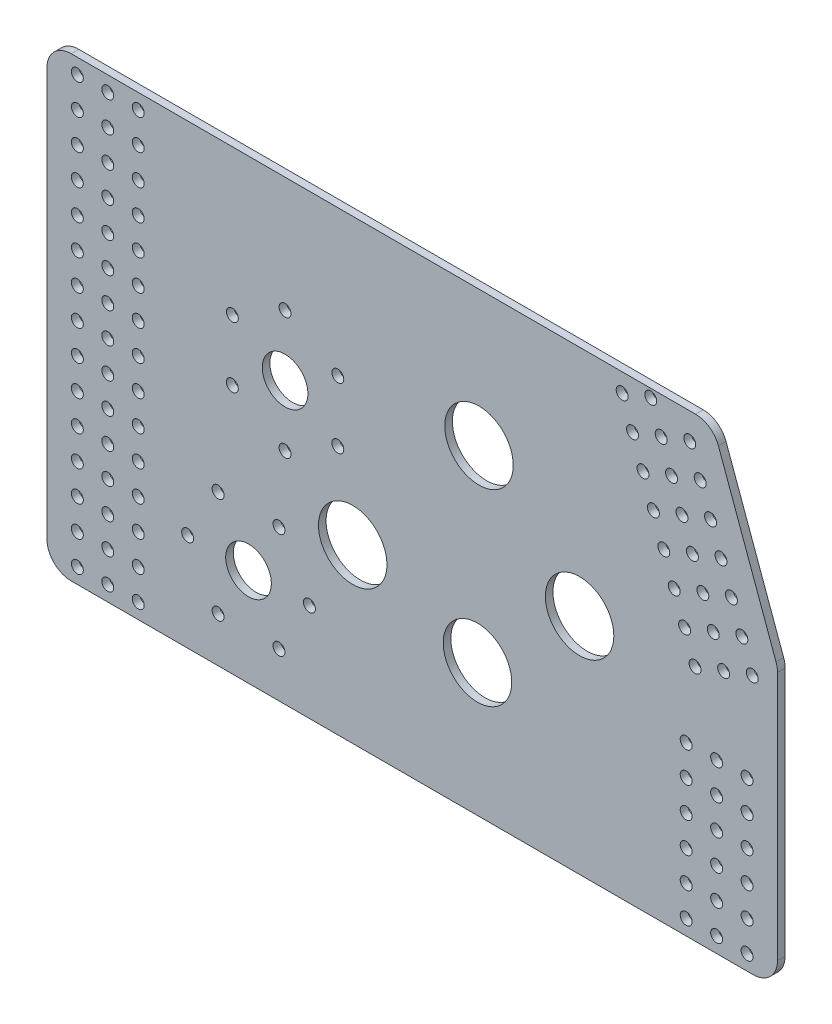
SolidWorks part; units mm, degrees
ref_plane "Front Plane" through (0, 0, 0) normal (0, 0, 1) x (1, 0, 0)
ref_plane "Top Plane" through (0, 0, 0) normal (0, 1, 0) x (1, 0, 0)
ref_plane "Right Plane" through (0, 0, 0) normal (1, 0, 0) x (0, 0, -1)
sketch "Sketch1" plane through (0, 0, 0) normal (0, 0, 1) x (1, 0, 0)
  line B0 (-152.4, 0) -> (152.4, 0)
  line B1 (152.4, 0) -> (152.4, 116.0843)
  line B2 (152.4, 116.0843) -> (125.3149, 190.5)
  line B3 (125.3149, 190.5) -> (-152.4, 190.5)
  line B4 (-152.4, 190.5) -> (-152.4, 0)
  circle B5 centre (-139.7, 184.15) radius 2.4892
  circle B6 centre (-127, 184.15) radius 2.4892
  circle B7 centre (-114.3, 184.15) radius 2.4892
  circle B8 centre (-127, 171.45) radius 2.4892
  circle B9 centre (-114.3, 171.45) radius 2.4892
  circle B10 centre (-127, 158.75) radius 2.4892
  circle B11 centre (-114.3, 158.75) radius 2.4892
  circle B12 centre (-127, 146.05) radius 2.4892
  circle B13 centre (-114.3, 146.05) radius 2.4892
  circle B14 centre (-127, 133.35) radius 2.4892
  circle B15 centre (-114.3, 133.35) radius 2.4892
  circle B16 centre (-127, 120.65) radius 2.4892
  circle B17 centre (-114.3, 120.65) radius 2.4892
  circle B18 centre (-127, 107.95) radius 2.4892
  circle B19 centre (-114.3, 107.95) radius 2.4892
  circle B20 centre (-127, 95.25) radius 2.4892
  circle B21 centre (-114.3, 95.25) radius 2.4892
  circle B22 centre (-127, 82.55) radius 2.4892
  circle B23 centre (-114.3, 82.55) radius 2.4892
  circle B24 centre (-127, 69.85) radius 2.4892
  circle B25 centre (-114.3, 69.85) radius 2.4892
  circle B26 centre (-127, 57.15) radius 2.4892
  circle B27 centre (-114.3, 57.15) radius 2.4892
  circle B28 centre (-127, 44.45) radius 2.4892
  circle B29 centre (-114.3, 44.45) radius 2.4892
  circle B30 centre (-127, 31.75) radius 2.4892
  circle B31 centre (-114.3, 31.75) radius 2.4892
  circle B32 centre (-127, 19.05) radius 2.4892
  circle B33 centre (-114.3, 19.05) radius 2.4892
  circle B34 centre (-127, 6.35) radius 2.4892
  circle B35 centre (-114.3, 6.35) radius 2.4892
  circle B36 centre (-139.7, 171.45) radius 2.4892
  circle B37 centre (-139.7, 158.75) radius 2.4892
  circle B38 centre (-139.7, 146.05) radius 2.4892
  circle B39 centre (-139.7, 133.35) radius 2.4892
  circle B40 centre (-139.7, 120.65) radius 2.4892
  circle B41 centre (-139.7, 107.95) radius 2.4892
  circle B42 centre (-139.7, 95.25) radius 2.4892
  circle B43 centre (-139.7, 82.55) radius 2.4892
  circle B44 centre (-139.7, 69.85) radius 2.4892
  circle B45 centre (-139.7, 57.15) radius 2.4892
  circle B46 centre (-139.7, 44.45) radius 2.4892
  circle B47 centre (-139.7, 31.75) radius 2.4892
  circle B48 centre (-139.7, 19.05) radius 2.4892
  circle B49 centre (-139.7, 6.35) radius 2.4892
  circle B50 centre (87.5907, 182.7494) radius 2.4892
  circle B51 centre (99.5248, 187.093) radius 2.4892
  circle B52 centre (115.8026, 179.5026) radius 2.4892
  circle B53 centre (91.9344, 170.8153) radius 2.4892
  circle B54 centre (103.8685, 175.1589) radius 2.4892
  circle B55 centre (120.1462, 167.5685) radius 2.4892
  circle B56 centre (96.278, 158.8812) radius 2.4892
  circle B57 centre (108.2121, 163.2248) radius 2.4892
  circle B58 centre (124.4899, 155.6344) radius 2.4892
  circle B59 centre (100.6217, 146.9471) radius 2.4892
  circle B60 centre (112.5558, 151.2907) radius 2.4892
  circle B61 centre (128.8335, 143.7003) radius 2.4892
  circle B62 centre (104.9653, 135.013) radius 2.4892
  circle B63 centre (116.8994, 139.3566) radius 2.4892
  circle B64 centre (133.1772, 131.7662) radius 2.4892
  circle B65 centre (109.309, 123.0789) radius 2.4892
  circle B66 centre (121.2431, 127.4226) radius 2.4892
  circle B67 centre (137.5208, 119.8321) radius 2.4892
  circle B68 centre (113.6526, 111.1448) radius 2.4892
  circle B69 centre (125.5867, 115.4885) radius 2.4892
  circle B70 centre (141.8645, 107.898) radius 2.4892
  circle B71 centre (117.9963, 99.2107) radius 2.4892
  circle B72 centre (129.9304, 103.5544) radius 2.4892
  circle B73 centre (146.2081, 95.9639) radius 2.4892
  circle B74 centre (114.3, 69.85) radius 2.4892
  circle B75 centre (127, 69.85) radius 2.4892
  circle B76 centre (139.7, 69.85) radius 2.4892
  circle B77 centre (114.3, 57.15) radius 2.4892
  circle B78 centre (127, 57.15) radius 2.4892
  circle B79 centre (139.7, 57.15) radius 2.4892
  circle B80 centre (114.3, 44.45) radius 2.4892
  circle B81 centre (127, 44.45) radius 2.4892
  circle B82 centre (139.7, 44.45) radius 2.4892
  circle B83 centre (114.3, 31.75) radius 2.4892
  circle B84 centre (127, 31.75) radius 2.4892
  circle B85 centre (139.7, 31.75) radius 2.4892
  circle B86 centre (114.3, 19.05) radius 2.4892
  circle B87 centre (127, 19.05) radius 2.4892
  circle B88 centre (139.7, 19.05) radius 2.4892
  circle B89 centre (114.3, 6.35) radius 2.4892
  circle B90 centre (127, 6.35) radius 2.4892
  circle B91 centre (139.7, 6.35) radius 2.4892
  circle B92 centre (11.8508, 132.0168) radius 14.2875
  circle B93 centre (-24.8197, 71.7449) radius 14.2875
  circle B94 centre (57.6351, 95.7125) radius 14.2875
  circle B95 centre (23.7546, 49.6787) radius 14.2875
  circle B96 centre (-65.2702, 36.9534) radius 9.525
  circle B97 centre (-65.2702, 106.5494) radius 9.525
  circle B98 centre (-65.2702, 131.9494) radius 2.4892
  circle B99 centre (-65.2702, 11.5534) radius 2.4892
  circle B100 centre (-43.2731, 119.2494) radius 2.4892
  circle B101 centre (-43.2731, 93.8494) radius 2.4892
  circle B102 centre (-65.2702, 81.1494) radius 2.4892
  circle B103 centre (-87.2672, 93.8494) radius 2.4892
  circle B104 centre (-87.2672, 119.2494) radius 2.4892
  circle B105 centre (-87.2672, 24.2534) radius 2.4892
  circle B106 centre (-87.2672, 49.6534) radius 2.4892
  circle B107 centre (-65.2702, 62.3534) radius 2.4892
  circle B108 centre (-43.2731, 49.6534) radius 2.4892
  circle B109 centre (-43.2731, 24.2534) radius 2.4892
sketch_block_instance "Block-InnerPlate-1"
sketch_block "Block-InnerPlate" parameters "D1"=4.9784, "D7"=4.9784, "D8"=4.9784, "D9"=4.9784, "D11"=4.9784, "D12"=4.9784, "D13"=4.9784, "D15"=19.05, "D16"=19.05, "D17"=28.575, "D18"=28.575, "D19"=28.575, "D20"=28.575, "D21"=4.9784, "D22"=4.9784, "D2"=6.35, "D3"=12.7, "D4"=12.7, "D5"=12.7, "D6"=6.35, "D10"=12.7, "D14"=12.7, "D23"=25.4, "D24"=25.4
extrude "Boss-Extrude1" add sketch "Sketch1" along normal blind 3.175
sketch "Sketch2" plane through (0, 0, 3.175) normal (0, 0, 1) x (1, 0, 0)
  circle A0 centre (146.2081, 95.9639) radius 2.4892
  dimension "D1" = 4.9784
extrude "Boss-Extrude2" add sketch "Sketch2" against normal blind 3.175
fillet "Fillet1" radius 10.16 5 edges at (-152.4, 0, 1.5875) (152.4, 0, 1.5875) (152.4, 116.0843, 1.5875) (125.3149, 190.5, 1.5875) (-152.4, 190.5, 1.5875)
sketch "Sketch3" plane through (0, 0, 3.175) normal (0, 0, 1) x (1, 0, 0)
  line L0 (-65.2702, 106.5494) -> (-39.8702, 106.5494) construction
  line L1 (-65.2702, 36.9534) -> (-39.8702, 36.9534) construction
  circle A0 centre (-65.2702, 106.5494) radius 9.525
  circle A1 centre (-39.8702, 106.5494) radius 2.4892
  circle A2 centre (-52.5702, 84.5524) radius 2.4892
  circle A3 centre (-77.9702, 84.5524) radius 2.4892
  circle A4 centre (-90.6702, 106.5494) radius 2.4892
  circle A5 centre (-77.9702, 128.5465) radius 2.4892
  circle A6 centre (-52.5702, 128.5465) radius 2.4892
  circle A7 centre (-65.2702, 36.9534) radius 9.525
  circle A8 centre (-39.8702, 36.9534) radius 2.4892
  circle A9 centre (-52.5702, 14.9564) radius 2.4892
  circle A10 centre (-77.9702, 14.9564) radius 2.4892
  circle A11 centre (-90.6702, 36.9534) radius 2.4892
  circle A12 centre (-77.9702, 58.9505) radius 2.4892
  circle A13 centre (-52.5702, 58.9505) radius 2.4892
  dimension "D1" = 19.05
  dimension "D2" = 4.9784
  dimension "D7" = 19.05
  dimension "D8" = 4.9784
  dimension "D3" = 25.4
  dimension "D5" = 25.4
  dimension "D6" = 25.4
  dimension "D9" = 25.4
  dimension "D11" = 25.4
  dimension "D4" = 6
  dimension "D10" = 6
extrude "Cut-Extrude1" cut sketch "Sketch3" against normal blind 3.175
sketch "Sketch4" plane through (0, 0, 3.175) normal (0, 0, 1) x (1, 0, 0)
  circle A0 centre (-65.2702, 131.9494) radius 2.4892
  circle A1 centre (-43.2731, 119.2494) radius 2.4892
  circle A2 centre (-43.2731, 93.8494) radius 2.4892
  circle A3 centre (-65.2702, 81.1494) radius 2.4892
  circle A4 centre (-87.2672, 93.8494) radius 2.4892
  circle A5 centre (-87.2672, 119.2494) radius 2.4892
  circle A6 centre (-65.2702, 62.3534) radius 2.4892
  circle A7 centre (-43.2731, 49.6534) radius 2.4892
  circle A8 centre (-43.2731, 24.2534) radius 2.4892
  circle A9 centre (-65.2702, 11.5534) radius 2.4892
  circle A10 centre (-87.2672, 24.2534) radius 2.4892
  circle A11 centre (-87.2672, 49.6534) radius 2.4892
  dimension "D1" = 4.9784
  dimension "D2" = 4.9784
  dimension "D3" = 4.9784
  dimension "D4" = 4.9784
  dimension "D5" = 4.9784
  dimension "D6" = 4.9784
  dimension "D7" = 4.9784
  dimension "D8" = 4.9784
  dimension "D9" = 4.9784
  dimension "D10" = 4.9784
  dimension "D11" = 4.9784
  dimension "D12" = 4.9784
extrude "Boss-Extrude3" add sketch "Sketch4" against normal blind 3.175
sketch "Sketch6" plane through (0, 0, 3.175) normal (0, 0, 1) x (1, 0, 0)
  circle A0 centre (23.7546, 49.6787) radius 14.2875 construction
  circle A1 centre (57.6351, 95.7125) radius 14.2875 construction
  circle A2 centre (11.8508, 132.0168) radius 14.2875 construction
  circle A3 centre (23.7546, 49.6787) radius 14.2875
  circle A4 centre (57.6351, 95.7125) radius 14.2875
  circle A5 centre (11.8508, 132.0168) radius 14.2875
  circle A6 centre (-39.8702, 36.9534) radius 2.4892 construction
  circle A7 centre (-52.5702, 14.9564) radius 2.4892 construction
  circle A8 centre (-77.9702, 14.9564) radius 2.4892 construction
  circle A9 centre (-65.2702, 36.9534) radius 9.525 construction
  circle A10 centre (-90.6702, 36.9534) radius 2.4892 construction
  circle A11 centre (-52.5702, 58.9505) radius 2.4892 construction
  circle A12 centre (-77.9702, 58.9505) radius 2.4892 construction
  circle A13 centre (-52.5702, 84.5524) radius 2.4892 construction
  circle A14 centre (-77.9702, 84.5524) radius 2.4892 construction
  circle A15 centre (-90.6702, 106.5494) radius 2.4892 construction
  circle A16 centre (-65.2702, 106.5494) radius 9.525 construction
  circle A17 centre (-39.8702, 106.5494) radius 2.4892 construction
  circle A18 centre (-52.5702, 128.5465) radius 2.4892 construction
  circle A19 centre (-77.9702, 128.5465) radius 2.4892 construction
  circle A20 centre (-39.8702, 36.9534) radius 2.4892
  circle A21 centre (-52.5702, 14.9564) radius 2.4892
  circle A22 centre (-77.9702, 14.9564) radius 2.4892
  circle A23 centre (-65.2702, 36.9534) radius 9.525
  circle A24 centre (-90.6702, 36.9534) radius 2.4892
  circle A25 centre (-52.5702, 58.9505) radius 2.4892
  circle A26 centre (-77.9702, 58.9505) radius 2.4892
  circle A27 centre (-52.5702, 84.5524) radius 2.4892
  circle A28 centre (-77.9702, 84.5524) radius 2.4892
  circle A29 centre (-90.6702, 106.5494) radius 2.4892
  circle A30 centre (-65.2702, 106.5494) radius 9.525
  circle A31 centre (-39.8702, 106.5494) radius 2.4892
  circle A32 centre (-52.5702, 128.5465) radius 2.4892
  circle A33 centre (-77.9702, 128.5465) radius 2.4892
extrude "Boss-Extrude4" add sketch "Sketch6" against normal up to surface (3.175 mm away) up to face at (-37.381, 36.9534, 0)
sketch "Sketch5" plane through (0, 0, 3.175) normal (0, 0, 1) x (1, 0, 0)
  circle A1 centre (-24.8197, 71.7449) radius 14.2875
  circle A2 centre (-24.8197, 71.7449) radius 13.97
  circle A3 centre (27.2348, 55.2349) radius 40.64
  circle A4 centre (27.2348, 55.2349) radius 14.2875
  circle A5 centre (27.2348, 55.2349) radius 22.86
  circle A6 centre (69.8319, 93.3349) radius 34.29
  circle A7 centre (69.8319, 93.3349) radius 14.2875
  circle A8 centre (69.8319, 93.3349) radius 12.7
  circle A9 centre (27.8642, 133.9749) radius 45.72
  circle A10 centre (27.8642, 133.9749) radius 14.2875
  circle A11 centre (-24.8197, 71.7449) radius 14.2875 construction
  point P1 (-24.2973, 73.5767)
  dimension "D1" = 27.94
  dimension "D2" = 81.28
  dimension "D3" = 28.575
  dimension "D4" = 45.72
  dimension "D5" = 68.58
  dimension "D6" = 28.575
  dimension "D7" = 25.4
  dimension "D8" = 91.44
  dimension "D12" = 28.575
  dimension "D9" = 16.51
  dimension "D10" = 38.1
  dimension "D11" = 40.64
extrude "Cut-Extrude2" cut sketch "Sketch5" against normal through all contours A4 | A9 A7 A8 | A8 | A7 A9 | A10 region at (69.8319, 93.3349, 3.175) region at (58.9004, 99.8547, 3.175) region at (60.198, 102.664, 3.175) region at (27.2348, 55.2349, 3.175) region at (27.8642, 133.9749, 3.175)
sketch "Sketch7" plane through (0, 0, 0) normal (0, 0, 1) x (1, 0, 0)
  circle A0 centre (-55.5743, 18.8147) radius 2.4892
  circle A1 centre (-24.8197, 71.7449) radius 14.2875
  circle A2 centre (-24.8197, 71.7449) radius 45.72 construction
  circle A3 centre (-53.0343, 117.0118) radius 7.62 construction
  circle A4 centre (-24.8197, 71.7449) radius 14.2875 construction
  circle A5 centre (-68.2743, 40.8118) radius 7.62 construction
  circle A6 centre (-53.0343, 117.0118) radius 32.5374 construction
  circle A7 centre (-80.9743, 18.8147) radius 2.4892
  circle A8 centre (-68.2743, 40.8118) radius 32.5374 construction
  circle A9 centre (-93.6743, 40.8118) radius 2.4892
  circle A10 centre (-68.2743, 40.8118) radius 9.525
  circle A11 centre (-42.8743, 40.8118) radius 2.4892
  circle A12 centre (-55.5743, 62.8088) radius 2.4892
  circle A13 centre (-80.9743, 62.8088) radius 2.4892
  circle A14 centre (-31.0373, 104.3118) radius 2.4892
  circle A15 centre (-53.0343, 91.6118) radius 2.4892
  circle A16 centre (-75.0314, 104.3118) radius 2.4892
  circle A17 centre (-53.0343, 117.0118) radius 9.525
  circle A18 centre (-31.0373, 129.7118) radius 2.4892
  circle A19 centre (-53.0343, 142.4118) radius 2.4892
  circle A20 centre (-75.0314, 129.7118) radius 2.4892
  point P11 (0, 0)
  point P14 (0, 0)
  point P16 (0, 0)
  point P17 (-67.0161, 40.8118)
  point P18 (0, 0)
  point P20 (0, 0)
  point P22 (-158.2157, 100.7486)
  point P24 (-191.0426, 113.8145)
  point P35 (0, 0)
  point P46 (-53.0343, 116.0744)
  point P47 (0, 0)
  point P48 (0, 0)
  point P49 (0, 0)
  point P50 (0, 0)
  point P51 (0, 0)
  point P52 (-74.5692, 128.9271)
  point P53 (0, 0)
  dimension "D1" = 91.44
  dimension "D2" = 15.24
  dimension "D5" = 65.0748
  dimension "D6" = 65.0748
  dimension "D7" = 19.05
  dimension "D8" = 4.9784
  dimension "D9" = 25.4
  dimension "D10" = 25.4
  dimension "D11" = 25.4
  dimension "D14" = 25.4
  dimension "D15" = 25.4
  dimension "D16" = 25.4
  dimension "D17" = 25.4
  dimension "D18" = 25.4
  dimension "D19" = 19.05
  dimension "D20" = 4.9784
  dimension "D3" = 76.2
  dimension "D4" = 15.24
  dimension "D12" = 25.4
  dimension "D13" = 25.4
  dimension "D21" = 25.4
  dimension "D22" = 25.4
  dimension "D23" = 25.4
  dimension "D24" = 25.4
  dimension "D25" = 25.4
  dimension "D26" = 25.4
  dimension "D27" = 25.4
  dimension "D28" = 25.4
  dimension "D29" = 25.4
  dimension "D30" = 25.4
  dimension "D31" = 25.4
extrude "Cut-Extrude3" cut sketch "Sketch7" along normal through all contours A9 | A13 | A11 | A12 | A7 | A0 | A10 | A20 | A17 | A19 | A15 | A14 | A18 | A16 region at (-55.5743, 18.8147, 0) region at (-80.9743, 18.8147, 0) region at (-93.6743, 40.8118, 0) region at (-68.2743, 40.8118, 0) region at (-42.8743, 40.8118, 0) region at (-55.5743, 62.8088, 0) region at (-80.9743, 62.8088, 0) region at (-31.0373, 104.3118, 0) region at (-53.0343, 91.6118, 0) region at (-53.0343, 117.0118, 0) region at (-31.0373, 129.7118, 0) region at (-53.0343, 142.4118, 0) region at (-75.0314, 129.7118, 0)
